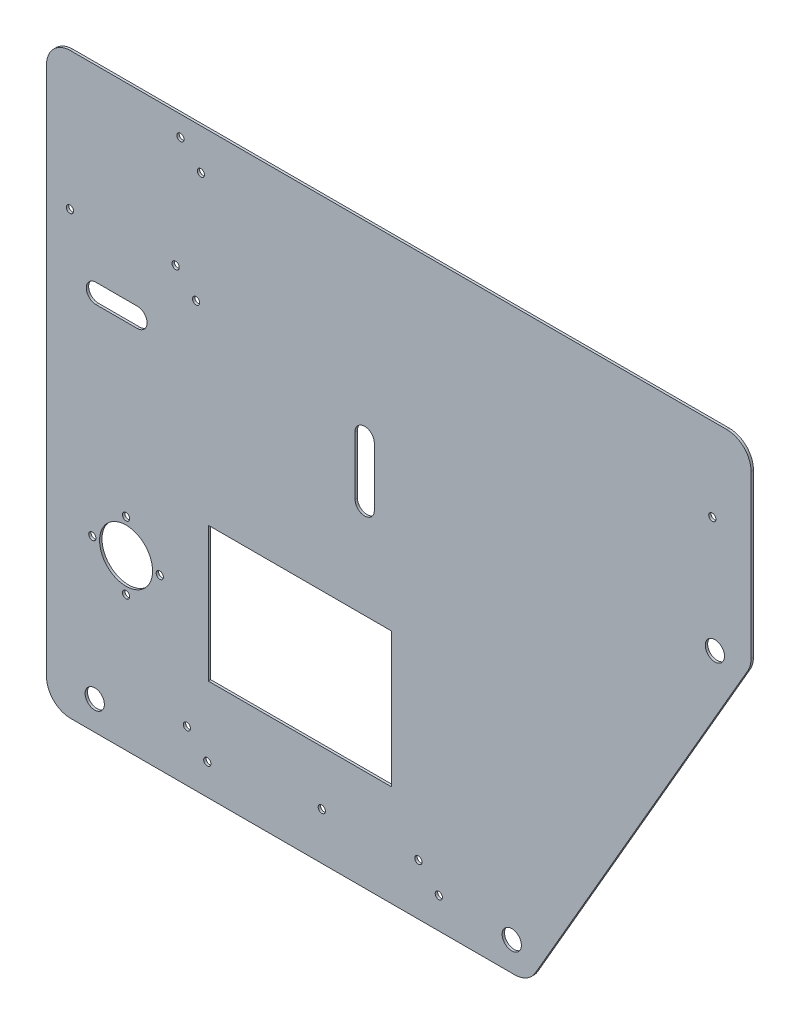
SolidWorks part; units mm, degrees
ref_plane "Front Plane" through (0, 0, 0) normal (0, 0, 1) x (1, 0, 0)
ref_plane "Top Plane" through (0, 0, 0) normal (0, 1, 0) x (1, 0, 0)
ref_plane "Right Plane" through (0, 0, 0) normal (1, 0, 0) x (0, 0, -1)
sketch "Sketch1" plane through (0, 0, 0) normal (0, 0, 1) x (1, 0, 0)
  line L0 (100, 80) -> (192.376, 80)
  line L1 (-100, -80) -> (100, -80)
  line L2 (-100, -80) -> (-100, 80)
  line L3 (-100, 80) -> (100, 80)
  line L4 (100, -80) -> (100, 80)
  line L5 (-100, -80) -> (100, 80) construction
  line L6 (-100, 80) -> (100, -80) construction
  line L7 (192.376, 80) -> (100, -80)
  line L8 (100, 80) -> (100, -80)
  line L10 (-100, 80) -> (192.376, 80)
  line L11 (-100, 80) -> (-100, 110)
  line L12 (-100, 110) -> (192.376, 110)
  line L13 (192.376, 80) -> (192.376, 110)
  point P0 (0, 0)
  dimension "D1" = 160
  dimension "D2" = 200
  dimension "D3" = 30
  dimension "D4" = 30
extrude "Boss-Extrude1" add sketch "Sketch1" along normal blind 1 contours L1 L4 L3 L2 | L7 L0 L4 | L11 L10 L13 L12 region at (0, 0, 0) region at (130.792, 26.6667, 0)
sketch "Sketch2" plane through (0, 0, 1) normal (0, 0, 1) x (1, 0, 0)
  line L0 (-100, -80) -> (100, -80) construction
  line L1 (192.376, 80) -> (100, -80) construction
  line L2 (-100, -80) -> (-100, 110) construction
  line L3 (-100, 110) -> (192.376, 110) construction
  line L4 (-79.5166, 78) -> (-62.3003, 78) construction
  line L7 (-100, -80) -> (-100, 110) construction
  line L8 (-29.8584, 15) -> (-29.8584, -35) construction
  line L9 (-79.5166, 82) -> (-62.3003, 82)
  line L10 (-79.5166, 74) -> (-62.3003, 74)
  line L11 (-32.8584, 18) -> (43.1416, 18)
  line L12 (-32.8584, 18) -> (-32.8584, -38)
  line L13 (-32.8584, -38) -> (43.1416, -38)
  line L14 (43.1416, 18) -> (43.1416, -38)
  line L15 (20.1416, 15) -> (-29.8584, 15) construction
  line L17 (40.1416, -35) -> (40.1416, 15) construction
  line L18 (32.0262, 82) -> (32.0262, 57.7776) construction
  line L19 (36.0262, 82) -> (36.0262, 57.7776)
  line L20 (28.0262, 82) -> (28.0262, 57.7776)
  circle A0 centre (93.0718, -68) radius 4
  circle A1 centre (177.3649, 78) radius 4
  circle A2 centre (-67, -10) radius 11
  circle A3 centre (-80, -68) radius 4
  circle A4 centre (-53, -10) radius 1.5
  circle A5 centre (-67, 4) radius 1.5
  circle A6 centre (-81, -10) radius 1.5
  circle A7 centre (-67, -24) radius 1.5
  circle A10 centre (32.0262, 70) radius 4 construction
  arc A11 (-79.5166, 82) -> (-79.5166, 74) centre (-79.5166, 78) ccw
  arc A12 (-62.3003, 74) -> (-62.3003, 82) centre (-62.3003, 78) ccw
  circle A32 centre (62.7961, -67.2426) radius 1.5
  circle A33 centre (54.3108, -58.7574) radius 1.5
  circle A34 centre (-33.2742, -67.2426) radius 1.5
  circle A35 centre (-41.7595, -58.7574) radius 1.5
  circle A36 centre (14.2259, -60.5) radius 1.5
  circle A37 centre (-37.9382, 96.1388) radius 1.5
  circle A38 centre (-46.4235, 104.6241) radius 1.5
  circle A39 centre (-90.2956, 102.8814) radius 1.5
  circle A40 centre (176.3056, 125.4889) radius 1.5
  arc A41 (36.0262, 82) -> (28.0262, 82) centre (32.0262, 82) ccw
  arc A42 (28.0262, 57.7776) -> (36.0262, 57.7776) centre (32.0262, 57.7776) ccw
  point P12 (-70.9085, 78)
  point P65 (32.0262, 69.8888)
  dimension "D3" = 8
  dimension "D4" = 8
  dimension "D9" = 22
  dimension "D10" = 8
  dimension "D12" = 3
  dimension "D13" = 3
  dimension "D14" = 3
  dimension "D15" = 3
  dimension "D16" = 14
  dimension "D20" = 4
  dimension "D22" = 8
  dimension "D23" = 3
  dimension "D24" = 20
  dimension "D25" = 3
  dimension "D1" = 12
  dimension "D2" = 12
  dimension "D5" = 32
  dimension "D6" = 12
  dimension "D7" = 33
  dimension "D8" = 70
  dimension "D11" = 12
  dimension "D17" = 14
  dimension "D18" = 14
  dimension "D19" = 14
  dimension "D21" = 40
  dimension "D26" = 3
  dimension "D27" = 3
  dimension "D28" = 8
  dimension "D29" = 3
extrude "Cut-Extrude1" cut sketch "Sketch2" against normal blind 3
sketch "Sketch3" plane through (0, 0, 1) normal (0, 0, 1) x (1, 0, 0)
  line L0 (192.376, 80) -> (192.376, 110) construction
  line L1 (-100, 110) -> (192.376, 110)
  line L2 (-100, 110) -> (-100, 160)
  line L3 (-100, 160) -> (192.376, 160)
  line L4 (192.376, 110) -> (192.376, 160)
  dimension "D1" = 50
extrude "Boss-Extrude2" add sketch "Sketch3" against normal blind 1
fillet "Fillet1" radius 10 5 edges at (100, -80, 0.5) (-100, -80, 0.5) (-100, 160, 0.5) (192.376, 160, 0.5) (192.376, 80, 0.5)
sketch "Sketch4" plane through (0, 0, 1) normal (0, 0, 1) x (1, 0, 0)
  circle A2 centre (-44.4423, 151.6241) radius 1.5
  circle A3 centre (-35.957, 143.1388) radius 1.5
  circle A4 centre (176.3056, 125.4889) radius 1.5
  dimension "D1" = 3
extrude "Cut-Extrude2" cut sketch "Sketch4" against normal blind 11
